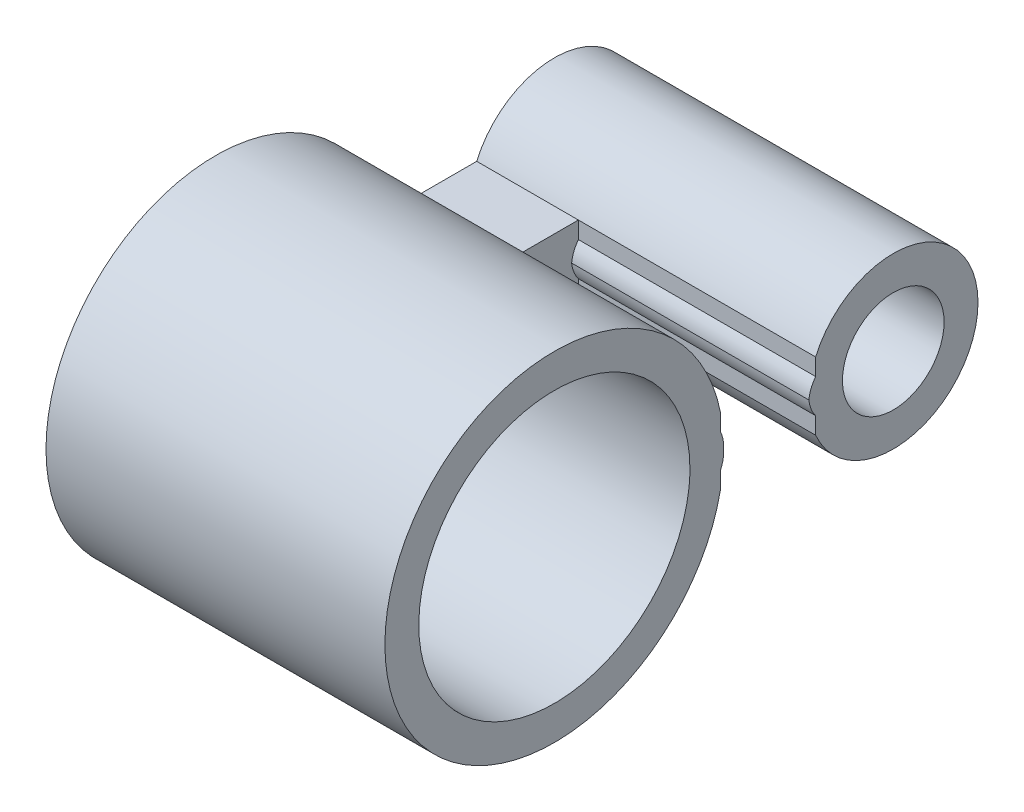
SolidWorks part; units mm, degrees
ref_plane "Front Plane" through (0, 0, 0) normal (0, 0, 1) x (1, 0, 0)
ref_plane "Top Plane" through (0, 0, 0) normal (0, 1, 0) x (1, 0, 0)
ref_plane "Right Plane" through (0, 0, 0) normal (1, 0, 0) x (0, 0, -1)
sketch "Sketch1" plane through (0, 0, 0) normal (1, 0, 0) x (0, 0, -1)
  line L1 (4.899, 1) -> (7.7087, 1)
  line L3 (10, 0) -> (10, 1)
  line L4 (7.7087, 1) -> (4.899, 1)
  line L5 (0, 0) -> (0, 1)
  line L7 (10, 0) -> (10, -1)
  line L8 (7.7087, -1) -> (4.899, -1)
  line L9 (0, 0) -> (0, -1)
  line L10 (3.873, 1) -> (3.873, 0.5)
  line L11 (3.873, 0.5) -> (8.882, 0.5)
  line L12 (8.882, 1) -> (8.882, 0.5)
  line L13 (7.7087, -1) -> (4.899, -1)
  line L14 (8.882, -1) -> (8.882, -0.5)
  line L15 (8.882, -0.5) -> (3.873, -0.5)
  line L16 (3.873, -1) -> (3.873, -0.5)
  arc A0 (4.899, 1) -> (4.899, -1) centre (0, 0) ccw
  arc A1 (7.7087, -1) -> (7.7087, 1) centre (10, 0) ccw
  arc A2 (3.873, 1) -> (3.873, -1) centre (0, 0) ccw
  arc A3 (8.882, -1) -> (8.882, 1) centre (10, 0) ccw
  dimension "D1" = 10
  dimension "D3" = 5
  dimension "D7" = 1
  dimension "D8" = 1
  dimension "D2" = 10
  dimension "D4" = 0.5
  dimension "D5" = 10
  dimension "D6" = 0.5
extrude "Boss-Extrude3" add sketch "Sketch1" along normal blind 10 contours L8 A1 L1 A0 A3 L14 L15 L16 A2 L10 L11 L12
sketch "Sketch2" plane through (0, 0, 0) normal (-1, 0, 0) x (0, 0, 1)
  line L1 (-8.5858, 0.5) -> (-3.9686, 0.5)
  line L3 (-8.5858, -0.5) -> (-3.9686, -0.5)
  arc A0 (-3.9686, -0.5) -> (-3.9686, 0.5) centre (0, 0) ccw
  arc A1 (-8.5858, 0.5) -> (-8.5858, -0.5) centre (-10, 0) ccw
extrude "Boss-Extrude4" add sketch "Sketch2" against normal blind 1 contours L1 A0 L3 A1
sketch "Sketch3" plane through (10, 0, 0) normal (1, 0, 0) x (0, 0, -1)
  circle A0 centre (0, 0) radius 4
  circle A1 centre (10, 0) radius 1.5
extrude "Cut-Extrude1" cut sketch "Sketch3" against normal blind 9 contours A0 | A1
sketch "Sketch4" plane through (10, 0, 0) normal (1, 0, 0) x (0, 0, -1)
  line L0 (4.899, 1) -> (7.7087, 1) construction
  line L1 (4.899, 1) -> (7.7087, 1)
  line L2 (4.899, 1) -> (4.899, -1)
  line L3 (4.899, -1) -> (7.7087, -1)
  line L4 (7.7087, 1) -> (7.7087, -1)
extrude "Cut-Extrude2" cut sketch "Sketch4" against normal blind 8
sketch "Sketch5" plane through (2, 0, 0) normal (1, 0, 0) x (0, 0, -1)
  line L0 (4.899, -1) -> (7.7087, -1) construction
  line L1 (4.899, 1) -> (7.7087, 1)
  line L2 (4.899, 1) -> (4.899, -1)
  line L3 (4.899, -1) -> (7.7087, -1)
  line L4 (7.7087, 1) -> (7.7087, -1)
  arc A0 (7.7087, -1) -> (7.7087, 1) centre (10, 0) ccw construction
extrude "Boss-Extrude5" add sketch "Sketch5" along normal blind 1
sketch "Sketch6" plane through (10, 0, 0) normal (1, 0, 0) x (0, 0, -1)
  line L0 (3.9686, 0.5) -> (4.9695, 0.5)
  line L1 (8.5858, 0.5) -> (3.9686, 0.5) construction
  line L2 (3.9686, -0.5) -> (4.9695, -0.5)
  line L3 (8.5858, 0.5) -> (7.5505, 0.5)
  line L4 (8.5858, -0.5) -> (7.5505, -0.5)
  arc A0 (3.9686, -0.5) -> (3.9686, 0.5) centre (0, 0) ccw
  arc A1 (4.9695, -0.5) -> (4.9695, 0.5) centre (0, 0) ccw
  arc A2 (8.5858, 0.5) -> (8.5858, -0.5) centre (10, 0) ccw
  arc A3 (7.5505, 0.5) -> (7.5505, -0.5) centre (10, 0) ccw
extrude "Boss-Extrude6" add sketch "Sketch6" against normal blind 8 contours A1 L0 A0 L2 | A3 L4 A2 L3
fillet "Fillet3" radius 1 4 edges at (6.5, 0.5, -4.9695) (6.5, -0.5, -4.9695) (6.5, -0.5, -7.5505) (6.5, 0.5, -7.5505)
